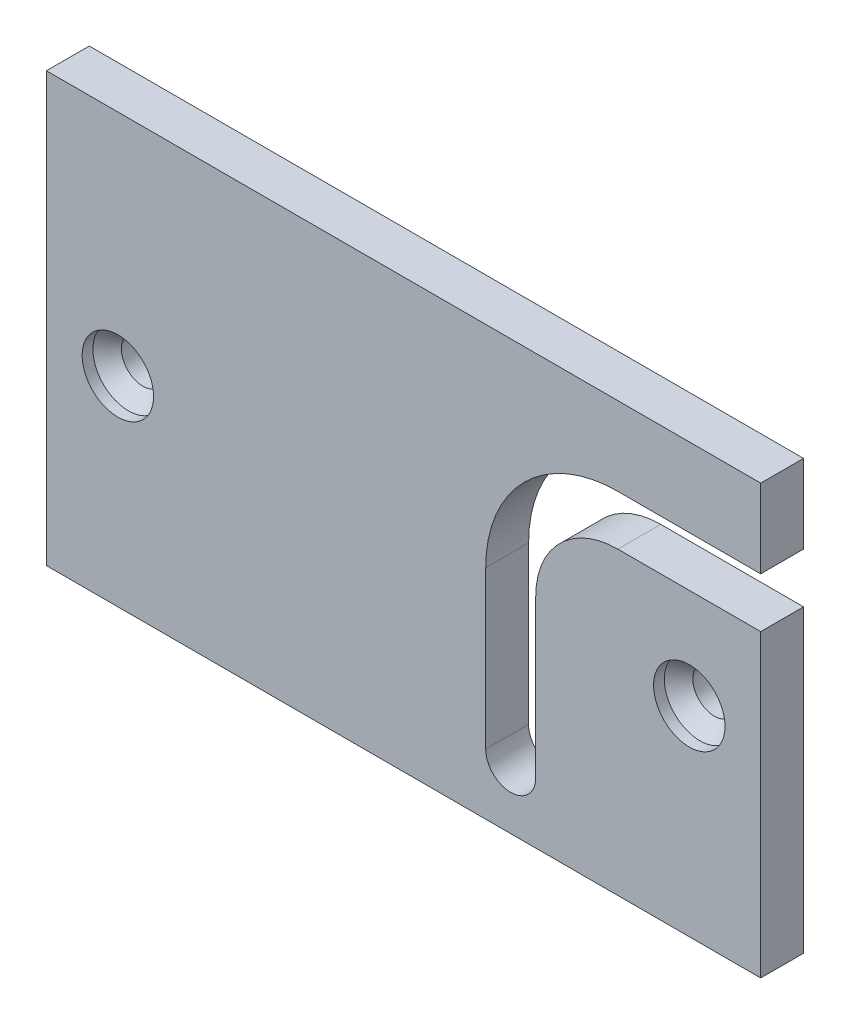
SolidWorks part; units mm, degrees
ref_plane "Спереди" through (0, 0, 0) normal (0, 0, 1) x (1, 0, 0)
ref_plane "Сверху" through (0, 0, 0) normal (0, 1, 0) x (1, 0, 0)
ref_plane "Справа" through (0, 0, 0) normal (1, 0, 0) x (0, 0, -1)
sketch "Эскиз1" plane through (0, 0, 0) normal (0, 0, 1) x (1, 0, 0)
  line L0 (0, 133.7222) -> (0, -128.0833) construction
  line L1 (-50, -30) -> (50, -30)
  line L2 (-50, -30) -> (-50, 30)
  line L3 (-50, 30) -> (50, 30)
  line L4 (50, -30) -> (50, 30)
  line L5 (-51.5556, 0) -> (155.4722, 0) construction
  dimension "D1" = 60
  dimension "D2" = 100
extrude "Бобышка-Вытянуть1" add sketch "Эскиз1" along normal mid plane 6
sketch "Эскиз2" plane through (0, 0, 3) normal (0, 0, 1) x (1, 0, 0)
  line L0 (-40, -2) -> (40, -2) construction
  line L1 (0, 0) -> (0, -2) construction
  circle A0 centre (-40, -2) radius 3
  circle A1 centre (40, -2) radius 3
  dimension "D2" = 6
  dimension "D1" = 80
  dimension "D3" = 2
extrude "Вырез-Вытянуть1" cut sketch "Эскиз2" against normal through all
sketch "Эскиз3" plane through (0, 0, 3) normal (0, 0, 1) x (1, 0, 0)
  circle A0 centre (-40, -2) radius 5
  circle A1 centre (40, -2) radius 5
  dimension "D1" = 10
extrude "Вырез-Вытянуть2" cut sketch "Эскиз3" against normal blind 1.5
chamfer "Фаска1" distance 2 angle 45 2 edges at (43, -2, 1.5) (-37, -2, 1.5)
sketch "Эскиз4" plane through (0, 0, 3) normal (0, 0, 1) x (1, 0, 0)
  line L0 (15, -21.5) -> (15, 0.5) construction
  line L1 (30, 15.5) -> (54.8252, 15.5) construction
  line L2 (50, -30) -> (50, 30) construction
  line L4 (18.5, -21.5) -> (18.5, 0.5)
  line L5 (30, 12) -> (54.8252, 12)
  line L6 (11.5, -21.5) -> (11.5, 0.5)
  line L7 (30, 19) -> (54.8252, 19)
  line L8 (0, 37.3071) -> (0, -38.4812) construction
  line L9 (-50, -30) -> (50, -30) construction
  line L10 (54.8252, 19) -> (54.8252, 12)
  line L11 (50, 30) -> (-50, 30) construction
  arc A0 (15, 0.5) -> (30, 15.5) centre (30, 0.5) cw construction
  arc A1 (18.5, 0.5) -> (30, 12) centre (30, 0.5) cw
  arc A2 (11.5, 0.5) -> (30, 19) centre (30, 0.5) cw
  arc A4 (18.5, -21.5) -> (11.5, -21.5) centre (15, -21.5) cw
  line M8 (50, -30) -> (50, 30)
  dimension "D1" = 15
  dimension "D6" = 5
  dimension "D2" = 35
  dimension "D3" = 11
  dimension "D4" = 3.5
  dimension "D5" = 3.5
extrude "Вырез-Вытянуть4" cut sketch "Эскиз4" against normal through all contours A4 L4 A1 L5 L7 A2 L6 M8 region at (15, -24.4153, 3)
mirror "Зеркальное отражение2" [suppressed] of bodies 107
